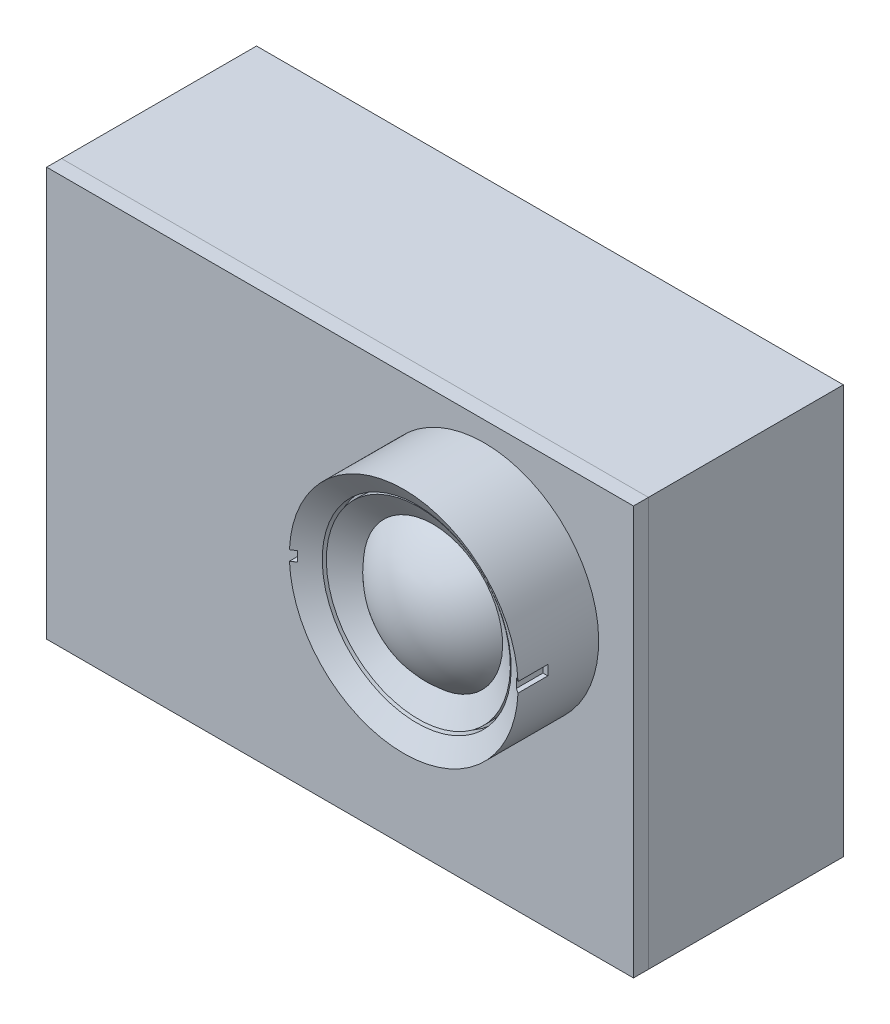
SolidWorks part; units mm, degrees
ref_plane "Front Plane" through (0, 0, 0) normal (0, 0, 1) x (1, 0, 0)
ref_plane "Top Plane" through (0, 0, 0) normal (0, 1, 0) x (1, 0, 0)
ref_plane "Right Plane" through (0, 0, 0) normal (1, 0, 0) x (0, 0, -1)
sketch "Sketch1" plane through (0, 0, 0) normal (0, 0, 1) x (1, 0, 0)
  line L1 (-29.5, -20.55) -> (29.5, -20.55)
  line L2 (-29.5, -20.55) -> (-29.5, 20.55)
  line L3 (-29.5, 20.55) -> (29.5, 20.55)
  line L4 (29.5, -20.55) -> (29.5, 20.55)
  line L5 (-29.5, -20.55) -> (29.5, 20.55) construction
  line L6 (-29.5, 20.55) -> (29.5, -20.55) construction
  point P0 (0, 0)
  dimension "D1" = 41.1
  dimension "D2" = 59
extrude "Boss-Extrude1" add sketch "Sketch1" along normal blind 19.6
sketch "Sketch2" plane through (0, 0, 19.6) normal (0, 0, 1) x (1, 0, 0)
  line L1 (-29.5, -20.55) -> (29.5, -20.55)
  line L2 (-29.5, -20.55) -> (-29.5, 20.55)
  line L3 (-29.5, 20.55) -> (29.5, 20.55)
  line L4 (29.5, -20.55) -> (29.5, 20.55)
  line L5 (-29.5, -20.55) -> (29.5, 20.55) construction
  line L6 (-29.5, 20.55) -> (29.5, -20.55) construction
  point P0 (0, 0)
extrude "Boss-Extrude2" add sketch "Sketch2" along normal blind 1.5 separate body
ref_plane "Plane1" through (14.5, 0, 0) normal (1, 0, 0) x (0, 0, -1)
sketch "Sketch4" plane through (14.5, 0, 0) normal (1, 0, 0) x (0, 0, -1)
  line L0 (-21.1, 7.05) -> (-29.6, 7.05)
  line L1 (-21.1, -20.55) -> (-21.1, 20.55) construction
  line L2 (-21.1, 7.05) -> (-21.1, 18.55)
  line L3 (-21.1, 18.55) -> (-29.2, 18.55)
  line L4 (-29.2, 18.55) -> (-27.8919, 16.55)
  line L5 (-27.8919, 16.55) -> (-26.8919, 16.55)
  line L6 (-26.8919, 16.55) -> (-26.8919, 16.3)
  line L7 (-26.8919, 16.3) -> (-27.7284, 16.3)
  line L8 (-27.7284, 16.3) -> (-26.2569, 14.05)
  line L9 (-29.6, 7.05) -> (-29.6, 9.5672) construction
  line L10 (-19.6, 20.55) -> (0, 20.55) construction
  arc A0 (-29.6, 7.05) -> (-26.2569, 14.05) centre (-20.6, 7.05) cw
  dimension "D5" = 9
  dimension "D1" = 11.5
  dimension "D2" = 8.1
  dimension "D3" = 7
  dimension "D4" = 9.5
  dimension "D6" = 0.25
  dimension "D7" = 1
  dimension "D8" = 8.5
  dimension "D9" = 2
revolve "Revolve1" add sketch "Sketch4" angle 360 about L0
sketch "Sketch5" plane through (0, 0, 21.1) normal (0, 0, 1) x (1, 0, 0)
  line L0 (3, 7.05) -> (26, 7.05) construction
  line L1 (26, 7.55) -> (26, 6.55)
  line L2 (26, 7.55) -> (25.5, 7.55)
  line L3 (25.5, 7.55) -> (25.5, 6.55)
  line L4 (25.5, 6.55) -> (26, 6.55)
  line L5 (14.5, 7.05) -> (14.5, 14.05) construction
  line L6 (14.5, -16.28) -> (14.5, 16.28) construction
  line L7 (3.5, 6.55) -> (3, 6.55)
  line L8 (3.5, 7.55) -> (3.5, 6.55)
  line L9 (3, 7.55) -> (3.5, 7.55)
  line L10 (3, 7.55) -> (3, 6.55)
  circle A0 centre (14.5, 7.05) radius 11.5 construction
  circle A1 centre (14.5, 7.05) radius 11.5 construction
  circle A2 centre (14.5, 7.05) radius 7 construction
  dimension "D1" = 1
  dimension "D2" = 0.5
extrude "Cut-Extrude2" cut sketch "Sketch5" against normal blind 3 from offset 8.1
